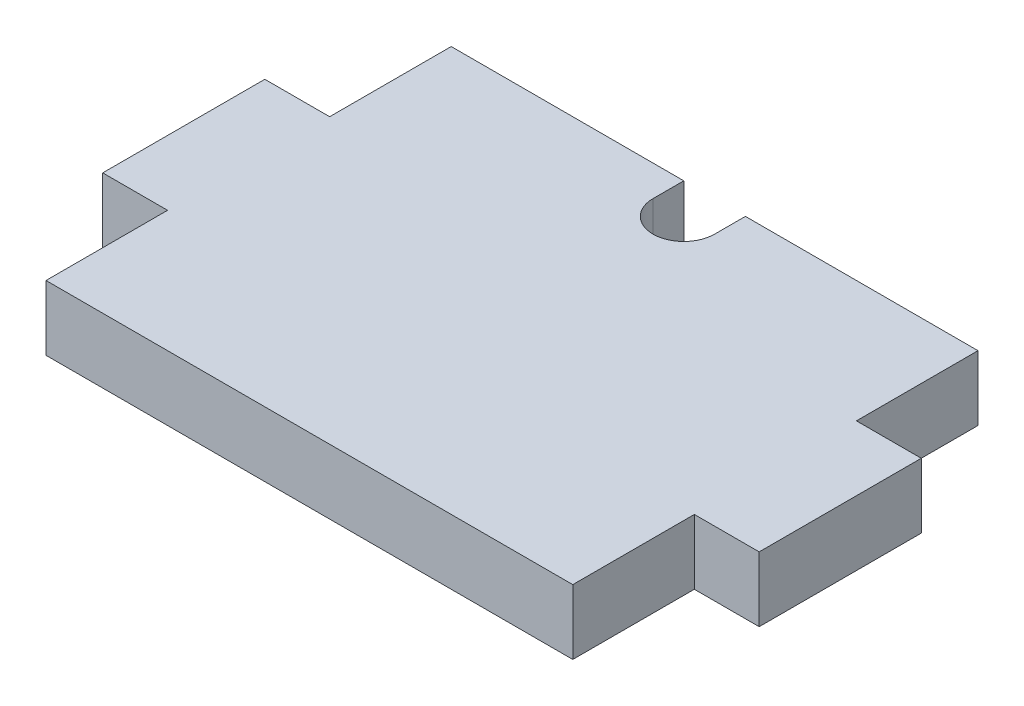
SolidWorks part; units mm, degrees
material "Maple"
ref_plane "Front Plane" through (0, 0, 0) normal (0, 0, 1) x (1, 0, 0)
ref_plane "Top Plane" through (0, 0, 0) normal (0, 1, 0) x (1, 0, 0)
ref_plane "Right Plane" through (0, 0, 0) normal (1, 0, 0) x (0, 0, -1)
sketch "Sketch1" plane through (0, 0, 0) normal (0, 1, 0) x (1, 0, 0)
  line L1 (0, 0) -> (32.5, 0)
  line L2 (0, 0) -> (0, -25)
  line L3 (0, -25) -> (32.5, -25)
  line L4 (32.5, 0) -> (32.5, -25)
  dimension "D1" = 32.5
  dimension "D2" = 25
extrude "Boss-Extrude1" add sketch "Sketch1" along normal blind 4
sketch "Sketch2" plane through (0, 4, 0) normal (0, 1, 0) x (1, 0, 0)
  line L0 (16.25, 0) -> (16.25, -25) construction
  line L1 (32.5, 0) -> (0, 0) construction
  line L2 (0, -25) -> (32.5, -25) construction
  line L4 (14.35, -1.9) -> (18.15, -1.9)
  line L5 (14.35, -1.9) -> (14.35, 0)
  line L6 (14.35, 0) -> (18.15, 0)
  line L7 (18.15, -1.9) -> (18.15, 0)
  circle A0 centre (16.25, -1.9) radius 1.9
  point P8 (18.15, -1.9)
  line M4 (32.5, 0) -> (0, 0)
  dimension "D1" = 3.8
extrude "Cut-Extrude5" cut sketch "Sketch2" against normal through all contours L0 L4 A0 | L0 A0 L4 | A0 L6 L5 | A0 L7 M4 | A0 L0 L4 | L4 L0 A0 region at (17.0564, 4, 1.0936) region at (14.7744, 4, 0.4244) region at (17.7256, 4, 0.4244) region at (15.4436, 4, 1.0936) region at (17.0564, 4, 2.7064) region at (15.4436, 4, 2.7064)
sketch "Sketch3" plane through (0, 4, 0) normal (0, 1, 0) x (1, 0, 0)
  line L0 (0, -12.5) -> (32.5, -12.5) construction
  line L1 (0, 0) -> (0, -25) construction
  line L2 (32.5, -25) -> (32.5, 0) construction
  line L4 (-4, -7.5) -> (0, -7.5)
  line L5 (-4, -7.5) -> (-4, -17.5)
  line L6 (-4, -17.5) -> (0, -17.5)
  line L7 (0, -7.5) -> (0, -17.5)
  line L8 (-4, -7.5) -> (0, -17.5) construction
  line L9 (-4, -17.5) -> (0, -7.5) construction
  line L10 (32.5, -7.5) -> (36.5, -7.5)
  line L11 (32.5, -7.5) -> (32.5, -17.5)
  line L12 (32.5, -17.5) -> (36.5, -17.5)
  line L13 (36.5, -7.5) -> (36.5, -17.5)
  line L14 (32.5, -7.5) -> (36.5, -17.5) construction
  line L15 (32.5, -17.5) -> (36.5, -7.5) construction
  point P6 (-2, -12.5)
  point P11 (34.5, -12.5)
  point P16 (44.8882, -18.5407)
  point P17 (35.3992, -18.2961)
  point P18 (-15.3718, -18.6874)
  point P19 (-5.0513, -18.345)
  dimension "D1" = 4
  dimension "D2" = 10
  dimension "D3" = 10
  dimension "D4" = 4
extrude "Boss-Extrude2" add sketch "Sketch3" against normal through all
equation "\"D3@Sketch3\"=\"D2@Sketch3\""
equation "\"D4@Sketch3\"=\"D1@Sketch3\""
